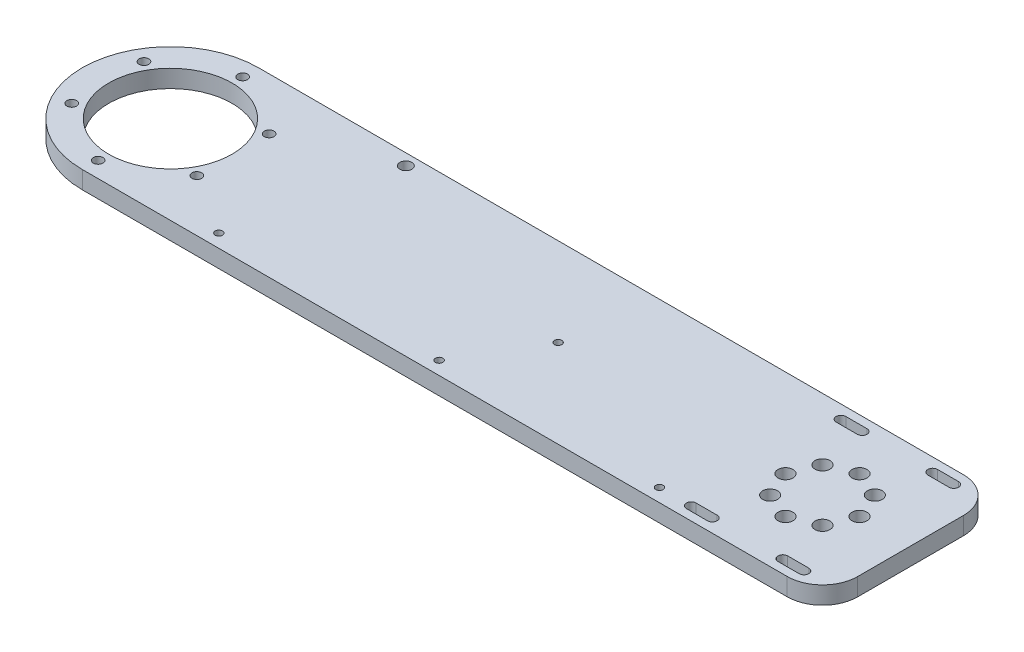
SolidWorks part; units mm, degrees
material "Lega 1060"
ref_plane "Piano frontale" through (0, 0, 0) normal (0, 0, 1) x (1, 0, 0)
ref_plane "Piano superiore" through (0, 0, 0) normal (0, 1, 0) x (1, 0, 0)
ref_plane "Piano destro" through (0, 0, 0) normal (1, 0, 0) x (0, 0, -1)
sketch "Schizzo1" plane through (0, 0, 0) normal (0, 1, 0) x (1, 0, 0)
  line L0 (0, 0) -> (50, 0) construction
  line L1 (-420, 50) -> (50, 50)
  line L2 (-420, 50) -> (-420, -50)
  line L3 (-420, -50) -> (50, -50)
  line L4 (50, 50) -> (50, -50)
  line L5 (-370, 0) -> (0, 0) construction
  circle A1 centre (-370, 0) radius 35
  point P8 (50, 0)
  dimension "D2" = 70
  dimension "D3" = 50
  dimension "D1" = 370
  dimension "D4" = 100
  dimension "D5" = 50
extrude "Estrusione-Estrusione1" add sketch "Schizzo1" along normal mid plane 10
hole_wizard "Foro per Vite M8-1" positions "Schizzo3" profile "Schizzo5" hole size "M8" standard "ISO" end condition through all
sketch "Schizzo3" plane through (0, 5, 0) normal (0, 1, 0) x (1, 0, 0)
  circle A0 centre (0, 0) radius 21 construction
  point P5 (21, 0)
  dimension "D1" = 42
sketch "Schizzo5" plane through (21, 5, 0) normal (1, 0, 0) x (0, 0, 1)
  line L0 (0, 0) -> (0, 10)
  line L1 (0, 10) -> (4.25, 10)
  line L2 (4.25, 10) -> (4.25, 0)
  line L5 (4.25, 0) -> (0, 0)
  line L11 (0, -6.35) -> (0, 107.95) construction
  dimension "Thru Hole Dia." = 8.5
  dimension "Thru Hole Depth" = 10
ref_axis "Assi1" through (0, 5.5, 0) along (0, -1, 0)
pattern_circular "RipetizioneCircolare1" count 8 over 360 about axis through (0, 5.5, 0) along (0, -1, 0) of "Foro per Vite M8-1"
sketch "Schizzo6" plane through (0, -5, 0) normal (0, -1, 0) x (1, 0, 0)
  circle A0 centre (0, 0) radius 28
  dimension "D1" = 56
extrude "Taglio-Estrusione1" cut sketch "Schizzo6" against normal blind 3
chamfer "Smusso1" distance 0.5 angle 45 1 edges at (0, -5, -28)
sketch "Schizzo7" plane through (0, 5, 0) normal (0, 1, 0) x (1, 0, 0)
  circle A0 centre (-370, 0) radius 41 construction
  circle A1 centre (-370, 41) radius 2.75
  dimension "D1" = 82
  dimension "D2" = 5.5
extrude "Taglio-Estrusione2" cut sketch "Schizzo7" against normal through all
pattern_circular "RipetizioneCircolare2" count 6 over 360 about axis through (-370, 5, 0) along (0, 1, 0) of "Taglio-Estrusione2"
fillet "Raccordo1" radius 20 2 edges at (50, 0, -50) (50, 0, 50)
fillet "Raccordo2" radius 50 2 edges at (-420, 0, -50) (-420, 0, 50)
sketch "Schizzo8" plane through (0, 5, 0) normal (0, 1, 0) x (1, 0, 0)
  line L0 (-370, -50) -> (30, -50) construction
  line L1 (-320, -35) -> (-50, -35)
  line L2 (-320, -35) -> (-320, -50)
  line L3 (-320, -50) -> (-50, -50)
  line L4 (-50, -35) -> (-50, -50)
  circle A0 centre (-370, 0) radius 35 construction
  dimension "D2" = 50
  dimension "D1" = 50
  dimension "D3" = 15
extrude "Estrusione-Estrusione2" [suppressed] add sketch "Schizzo8" along normal blind 50
sketch "Schizzo9" plane through (0, 5, 0) normal (0, 1, 0) x (1, 0, 0)
  line L0 (0, 42.5) -> (0, -42.5) construction
  line L1 (26, -42.5) -> (-26, -42.5) construction
  line L2 (26, -42.5) -> (26, 42.5) construction
  line L3 (26, 42.5) -> (-26, 42.5) construction
  line L4 (-26, -42.5) -> (-26, 42.5) construction
  line L5 (26, -42.5) -> (-26, 42.5) construction
  line L6 (26, 42.5) -> (-26, -42.5) construction
  line L7 (-32, 42.5) -> (-20, 42.5) construction
  line L8 (-32, 46.55) -> (-20, 46.55)
  line L9 (-32, 38.45) -> (-20, 38.45)
  line L10 (20, 42.5) -> (32, 42.5) construction
  line L11 (20, 46.55) -> (32, 46.55)
  line L12 (20, 38.45) -> (32, 38.45)
  line L13 (-32, -42.5) -> (-20, -42.5) construction
  line L16 (-32, -38.45) -> (-20, -38.45)
  line L17 (-32, -46.55) -> (-20, -46.55)
  line L18 (20, -42.5) -> (32, -42.5) construction
  line L19 (20, -38.45) -> (32, -38.45)
  line L20 (20, -46.55) -> (32, -46.55)
  arc A6 (-32, 46.55) -> (-32, 38.45) centre (-32, 42.5) ccw
  arc A7 (-20, 38.45) -> (-20, 46.55) centre (-20, 42.5) ccw
  arc A8 (20, 46.55) -> (20, 38.45) centre (20, 42.5) ccw
  arc A9 (32, 38.45) -> (32, 46.55) centre (32, 42.5) ccw
  arc A12 (-32, -38.45) -> (-32, -46.55) centre (-32, -42.5) ccw
  arc A13 (-20, -46.55) -> (-20, -38.45) centre (-20, -42.5) ccw
  arc A14 (20, -38.45) -> (20, -46.55) centre (20, -42.5) ccw
  arc A15 (32, -46.55) -> (32, -38.45) centre (32, -42.5) ccw
  point P0 (0, 0)
  point P10 (-26, 42.5)
  point P15 (26, 42.5)
  point P22 (-26, -42.5)
  point P29 (26, -42.5)
  dimension "D3" = 12
  dimension "D4" = 4.05
  dimension "D1" = 52
  dimension "D2" = 85
extrude "Taglio-Estrusione3" cut sketch "Schizzo9" along normal blind 4 from surface starting at face at (-336.8745, -5, -19.125)
sketch "Schizzo10" plane through (0, 5, 0) normal (0, 1, 0) x (1, 0, 0)
  line L0 (0, 0) -> (-370, 0) construction
  circle A0 centre (-150, 0) radius 2.1
  dimension "D1" = 4.2
  dimension "D2" = 150
extrude "Taglio-Estrusione4" cut sketch "Schizzo10" against normal through all
sketch "Schizzo11" plane through (0, 5, 0) normal (0, 1, 0) x (1, 0, 0)
  circle A0 centre (-280, 43.589) radius 3.4
  circle A1 centre (-370, 0) radius 35 construction
  dimension "D1" = 6.8
  dimension "D2" = 280
  dimension "D3" = 100
extrude "Taglio-Estrusione5" cut sketch "Schizzo11" against normal up to surface (10 mm away) up to face at (-150, -5, 2.1)
sketch "Schizzo12" plane through (0, 5, 0) normal (0, 1, 0) x (1, 0, 0)
  line L0 (-300, -42.5) -> (-50, -42.5) construction
  line L1 (-370, -50) -> (30, -50) construction
  circle A0 centre (-50, -42.5) radius 2.1
  circle A1 centre (-300, -42.5) radius 2.1
  circle A2 centre (-175, -42.5) radius 2.1
  dimension "D4" = 4.2
  dimension "D1" = 7.5
  dimension "D2" = 250
  dimension "D3" = 50
extrude "Taglio-Estrusione6" cut sketch "Schizzo12" against normal through all
sketch "Schizzo13" plane through (0, -1, 0) normal (0, -1, 0) x (-1, 0, 0)
  line L0 (32, -42.5) -> (20, -42.5) construction
  line L1 (32, -45.25) -> (20, -45.25)
  line L2 (32, -39.75) -> (20, -39.75)
  line L3 (-20, -42.5) -> (-32, -42.5) construction
  line L4 (-20, -45.25) -> (-32, -45.25)
  line L5 (-20, -39.75) -> (-32, -39.75)
  line L6 (-32, 42.5) -> (-20, 42.5) construction
  line L7 (-32, 45.25) -> (-20, 45.25)
  line L8 (-32, 39.75) -> (-20, 39.75)
  line L9 (20, 42.5) -> (32, 42.5) construction
  line L10 (20, 45.25) -> (32, 45.25)
  line L11 (20, 39.75) -> (32, 39.75)
  arc A0 (32, -45.25) -> (32, -39.75) centre (32, -42.5) ccw
  arc A1 (20, -39.75) -> (20, -45.25) centre (20, -42.5) ccw
  arc A2 (-20, -45.25) -> (-20, -39.75) centre (-20, -42.5) ccw
  arc A3 (-32, -39.75) -> (-32, -45.25) centre (-32, -42.5) ccw
  arc A4 (-32, 45.25) -> (-32, 39.75) centre (-32, 42.5) ccw
  arc A5 (-20, 39.75) -> (-20, 45.25) centre (-20, 42.5) ccw
  arc A6 (20, 45.25) -> (20, 39.75) centre (20, 42.5) ccw
  arc A7 (32, 39.75) -> (32, 45.25) centre (32, 42.5) ccw
  point P4 (26, -42.5)
  point P13 (-26, -42.5)
  point P18 (-26, 42.5)
  point P27 (26, 42.5)
  dimension "D1" = 5.5
extrude "Taglio-Estrusione7" cut sketch "Schizzo13" against normal through all
